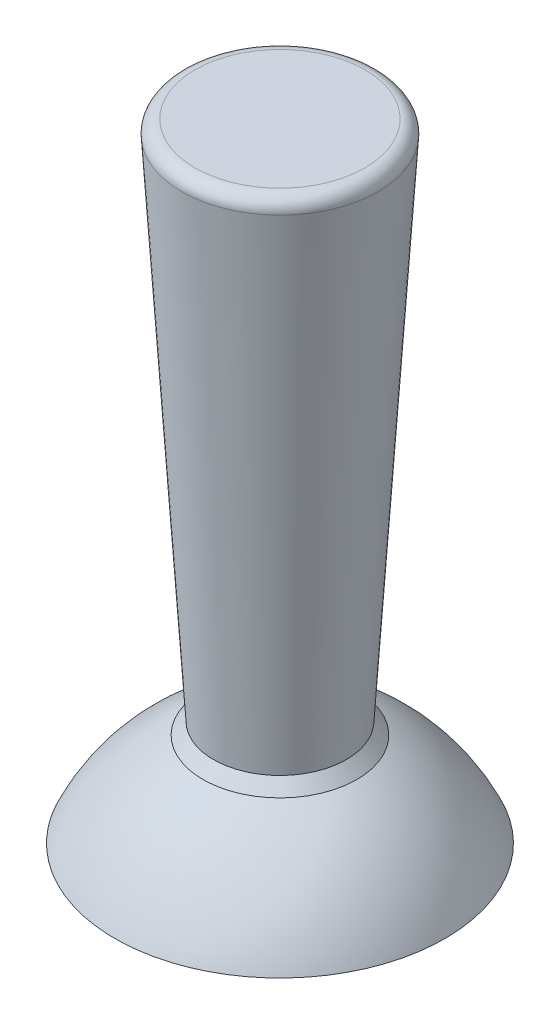
SolidWorks part; units mm, degrees
ref_plane "Front Plane" through (0, 0, 0) normal (0, 0, 1) x (1, 0, 0)
ref_plane "Top Plane" through (0, 0, 0) normal (0, 1, 0) x (1, 0, 0)
ref_plane "Right Plane" through (0, 0, 0) normal (1, 0, 0) x (0, 0, -1)
sketch "Sketch9" plane through (0, 0, 0) normal (0, 0, 1) x (1, 0, 0)
  line L2 (0, 0) -> (12.5, 0)
  line L3 (0, 0) -> (0, 7.5)
  line L5 (0, 7.5) -> (5, 7.5)
  arc A0 (5, 7.5) -> (12.5, 0) centre (-1.1716, -6.1716) cw
  dimension "D6" = 15
  dimension "D3" = 12.5
revolve "Revolve4" add sketch "Sketch9" angle 360 about L3
shell "Shell4" thickness 1 removed face at (0, 0, -12.5)
sketch "Sketch10" plane through (0, 0, 0) normal (0, 0, 1) x (1, 0, 0)
  line L0 (0, 7.5) -> (0, 47.5)
  line L1 (5, 7.5) -> (-5, 7.5) construction
  line L2 (0, 47.5) -> (7.5, 47.5)
  line L3 (7.5, 47.5) -> (5, 7.5)
  line L4 (5, 7.5) -> (0, 7.5)
  line L6 (0, 7.5) -> (2.75, 7.5)
  line L7 (0, 7.5) -> (0, 1.5)
  line L8 (0, 1.5) -> (2.75, 1.5)
  line L9 (2.75, 7.5) -> (2.75, 1.5)
  line L10 (2.75, 7.5) -> (5, 7.5)
  line L11 (2.75, 7.5) -> (2.75, 4.5)
  dimension "D1" = 40
  dimension "D2" = 7.5
  dimension "D3" = 6
  dimension "D4" = 2.75
revolve "Revolve5" add sketch "Sketch10" angle 360 about L0 region at (3.1667, 28.8333, 0) region at (1.375, 4.5, 0)
fillet "Fillet3" radius 1 1 edges at (0, 47.5, -7.5)
chamfer "Chamfer1" distance 0.5 angle 45 1 edges at (0, 7.5, -5) first distance on face at (0, 46.4376, -7.4336)
sketch "Sketch13" plane through (0, 0, 0) normal (0, 0, 1) x (1, 0, 0)
  line L0 (5, 7.5) -> (2.75, 4.5)
  line L1 (2.75, 4.5) -> (2.75, 7.5)
  line L2 (2.75, 7.5) -> (5, 7.5)
revolve "Revolve6" add sketch "Sketch13" angle 360 about L7
sketch "Sketch14" plane through (0, 1.5, 0) normal (0, -1, 0) x (1, 0, 0)
  ellipse E0 centre (0, 0) end of major axis (2.2, 0) minor radius 1.7
  dimension "D1" = 2.2
  dimension "D2" = 1.7
extrude "Cut-Extrude1" cut sketch "Sketch14" against normal blind 8
